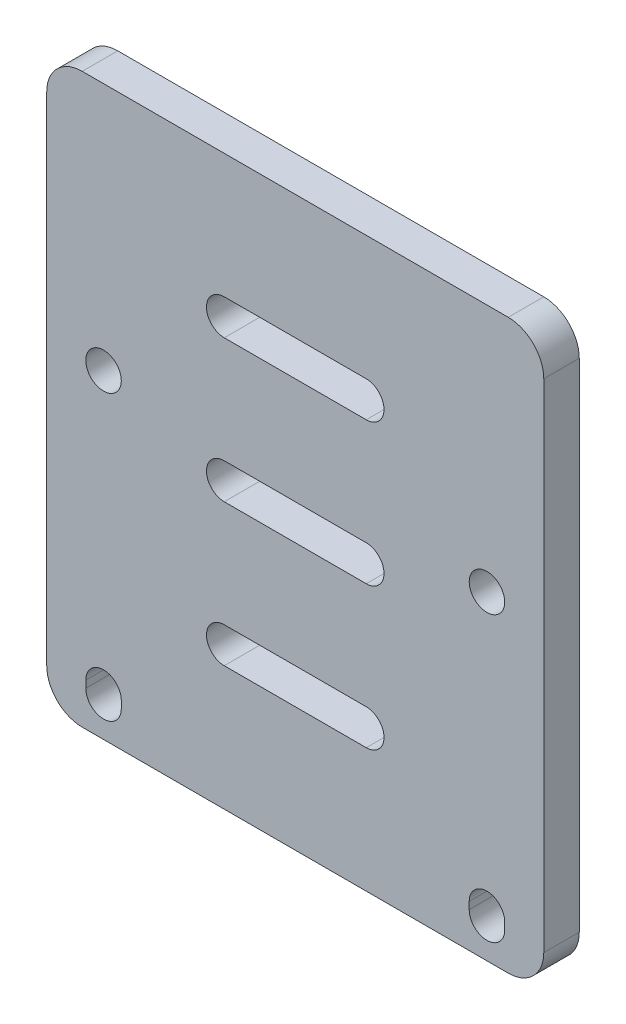
SolidWorks part; units mm, degrees
ref_plane "Front" through (0, 0, 0) normal (0, 0, 1) x (1, 0, 0)
ref_plane "Top" through (0, 0, 0) normal (0, 1, 0) x (1, 0, 0)
ref_plane "Right" through (0, 0, 0) normal (1, 0, 0) x (0, 0, -1)
sketch "Sketch4" plane through (0, 0, 0) normal (0, 0, 1) x (1, 0, 0)
  line L0 (-27, -34) -> (-27, -35) construction
  line L1 (-35, 40) -> (35, 40)
  line L2 (-35, 40) -> (-35, -40)
  line L3 (-35, -40) -> (35, -40)
  line L4 (35, 40) -> (35, -40)
  line L5 (-35, 40) -> (35, -40) construction
  line L6 (-35, -40) -> (35, 40) construction
  line L7 (-24.5, -34) -> (-24.5, -35)
  line L8 (-29.5, -34) -> (-29.5, -35)
  line L9 (0, -47.1607) -> (0, 39.6245) construction
  line L10 (27, -34) -> (27, -35) construction
  line L11 (24.5, -34) -> (24.5, -35)
  line L12 (29.5, -34) -> (29.5, -35)
  line L13 (-21.7344, 0) -> (13.0886, 0) construction
  line L14 (-15, 35) -> (15, 35) construction
  line L15 (-15, 35) -> (-15, -35) construction
  line L16 (-15, -35) -> (15, -35) construction
  line L17 (15, 35) -> (15, -35) construction
  line L18 (-15, 35) -> (15, -35) construction
  line L19 (-15, -35) -> (15, 35) construction
  circle A0 centre (-27, 5) radius 2.5
  arc A1 (-24.5, -34) -> (-29.5, -34) centre (-27, -34) ccw
  arc A2 (-29.5, -35) -> (-24.5, -35) centre (-27, -35) ccw
  arc A3 (24.5, -34) -> (29.5, -34) centre (27, -34) cw
  arc A4 (29.5, -35) -> (24.5, -35) centre (27, -35) cw
  circle A5 centre (27, 5) radius 2.5
  circle A6 centre (-15, 35) radius 1.5 construction
  circle A7 centre (15, 35) radius 1.5 construction
  circle A8 centre (15, -35) radius 1.5 construction
  circle A9 centre (-15, -35) radius 1.5 construction
  point P0 (0, 0)
  point P10 (-27, -34.5)
  point P19 (27, -34.5)
  point P28 (0, 0)
  dimension "D3" = 27
  dimension "D6" = 2.5
  dimension "D8" = 3
  dimension "D1" = 70
  dimension "D2" = 80
  dimension "D4" = 39
  dimension "D5" = 1
  dimension "D7" = 5
  dimension "D9" = 30
  dimension "D10" = 70
extrude "Boss-Extrude2" add sketch "Sketch4" along normal blind 5
fillet "Fillet1" radius 5 4 edges at (-35, -40, 2.5) (35, -40, 2.5) (35, 40, 2.5) (-35, 40, 2.5)
sketch "Sketch6" plane through (0, 0, 5) normal (0, 0, 1) x (1, 0, 0)
  line L3 (0, 17.5) -> (0, -2.5) construction
  line L4 (-2.5, 0) -> (2.5, 0) construction
  line L8 (-10, 20) -> (10, 20) construction
  line L9 (-10, 22.5) -> (10, 22.5)
  line L10 (-10, 17.5) -> (10, 17.5)
  line L11 (-10, -20) -> (10, -20) construction
  line L24 (-10, 0) -> (10, 0) construction
  line L25 (-10, 2.5) -> (10, 2.5)
  line L26 (-10, -2.5) -> (10, -2.5)
  line L27 (-10, -22.5) -> (10, -22.5)
  line L28 (-10, -17.5) -> (10, -17.5)
  arc A4 (-10, 22.5) -> (-10, 17.5) centre (-10, 20) ccw
  arc A5 (10, 17.5) -> (10, 22.5) centre (10, 20) ccw
  arc A17 (-10, 2.5) -> (-10, -2.5) centre (-10, 0) ccw
  arc A18 (10, -2.5) -> (10, 2.5) centre (10, 0) ccw
  arc A19 (-10, -22.5) -> (-10, -17.5) centre (-10, -20) cw
  arc A20 (10, -17.5) -> (10, -22.5) centre (10, -20) cw
  point P0 (0, 0)
  point P3 (0, 0)
  point P22 (0, 20)
  point P30 (0, -20)
  point P52 (0, 0)
  point P57 (0, 0)
  point P58 (0, 0)
  point P59 (-0.1564, -8.3117)
  point P60 (-30.0198, 10.6515)
  point P61 (0, 0)
  dimension "D4" = 2.5
  dimension "D5" = 20
  dimension "D7" = 2.5
  dimension "D3" = 20
  dimension "D6" = 20
  dimension "D8" = 20
extrude "Cut-Extrude1" cut sketch "Sketch6" against normal through all
